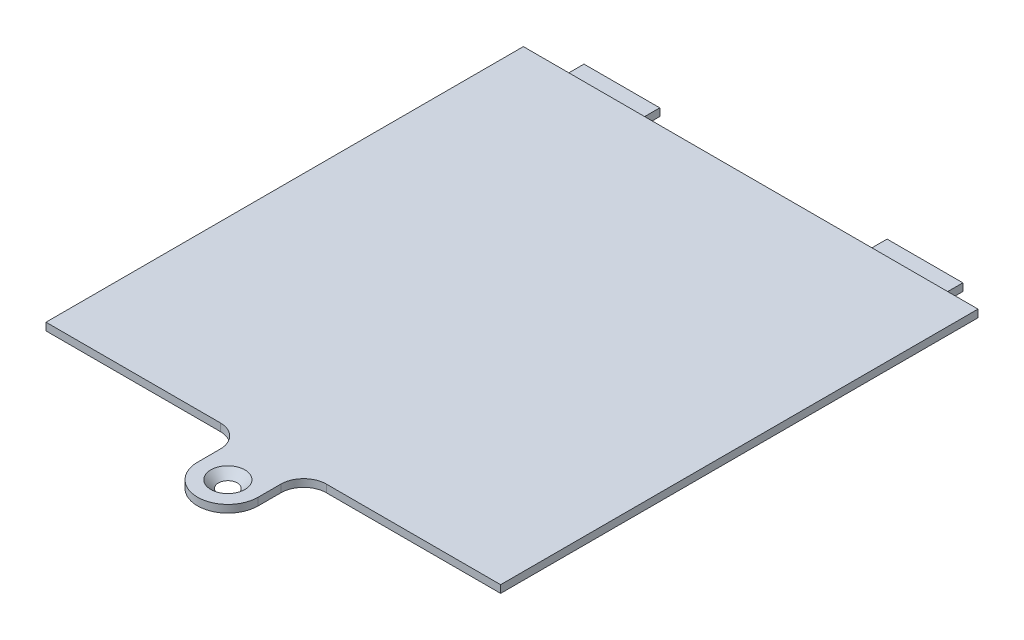
SolidWorks part; units mm, degrees
ref_plane "Front Plane" through (0, 0, 0) normal (0, 0, 1) x (1, 0, 0)
ref_plane "Top Plane" through (0, 0, 0) normal (0, 1, 0) x (1, 0, 0)
ref_plane "Right Plane" through (0, 0, 0) normal (1, 0, 0) x (0, 0, -1)
sketch "Sketch1" plane through (0, 0, 0) normal (0, 1, 0) x (1, 0, 0)
  line L0 (26, -6) -> (26, 0)
  line L1 (0, 0) -> (60, 0)
  line L2 (0, 0) -> (0, 63)
  line L3 (0, 63) -> (60, 63)
  line L4 (60, 0) -> (60, 63)
  line L5 (26, 0) -> (0, 0)
  line L6 (34, -6) -> (34, 0)
  line L7 (34, 0) -> (60, 0)
  circle A0 centre (30, -6) radius 4
  circle A1 centre (30, -6) radius 1.25
  dimension "D3" = 8
  dimension "D4" = 6
  dimension "D5" = 30
  dimension "D1" = 60
  dimension "D2" = 63
extrude "Boss-Extrude1" add sketch "Sketch1" along normal blind 1 contours L1 L4 L3 L2 | A0 L6 L1 L0 | A0 A1 region at (30, 0, 1.5686) region at (30, 0, 2.1131) region at (30, 0, -31.5)
fillet "Fillet1" radius 3 2 edges at (34, 0.5, 0) (26, 0.5, 0)
sketch "Sketch2" plane through (0, 0, 0) normal (0, -1, 0) x (-1, 0, 0)
  line L0 (0, 0) -> (0, 63) construction
  line L1 (-5, 61) -> (-15, 61)
  line L2 (-5, 61) -> (-5, 66)
  line L3 (-5, 66) -> (-15, 66)
  line L4 (-15, 61) -> (-15, 66)
  line L5 (-45, 61) -> (-55, 61)
  line L6 (-45, 61) -> (-45, 66)
  line L7 (-45, 66) -> (-55, 66)
  line L8 (-55, 61) -> (-55, 66)
  line L9 (-60, 0) -> (-60, 63) construction
  line L10 (0, 63) -> (-60, 63) construction
  dimension "D1" = 5
  dimension "D2" = 10
  dimension "D3" = 5
  dimension "D4" = 10
  dimension "D5" = 2
  dimension "D6" = 2
  dimension "D7" = 5
  dimension "D8" = 5
extrude "Boss-Extrude2" add sketch "Sketch2" along normal blind 1
chamfer "Chamfer1" distance 1 angle 45 2 edges at (50, 0, -61) (10, 0, -61)
chamfer "Chamfer2" distance 1 angle 45 1 edges at (30, 1, 7.25)
